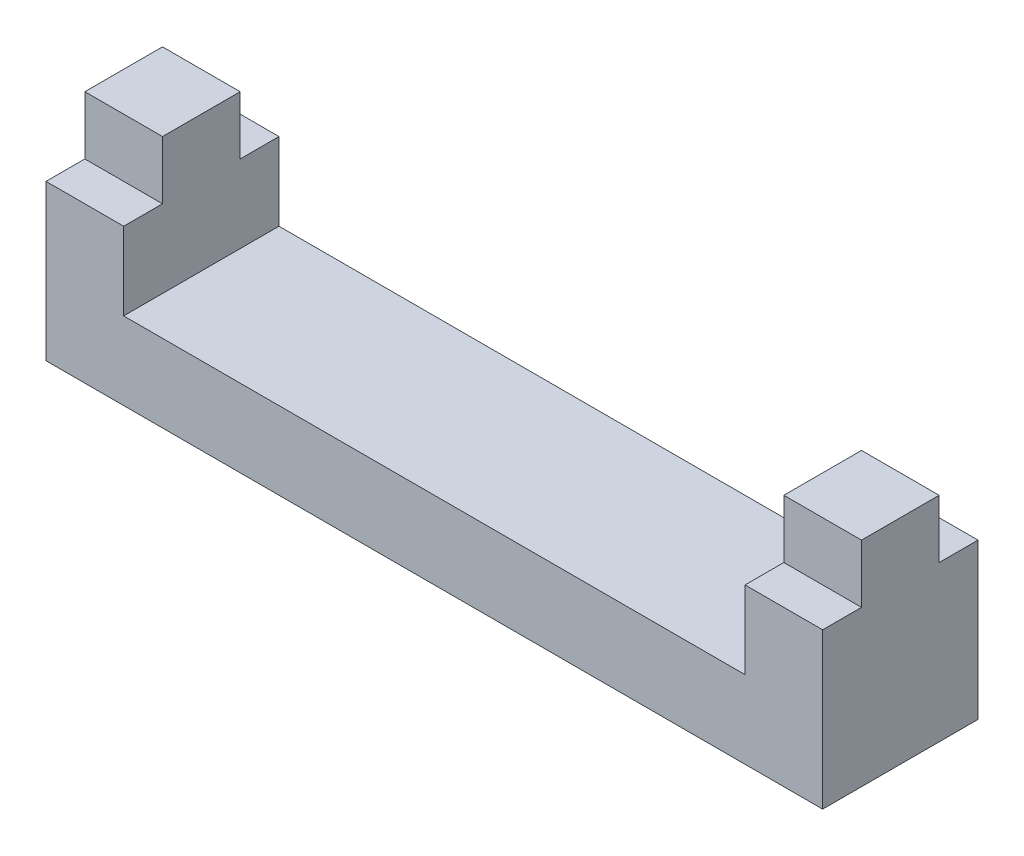
SolidWorks part; units mm, degrees
ref_plane "Front Plane" through (0, 0, 0) normal (0, 0, 1) x (1, 0, 0)
ref_plane "Top Plane" through (0, 0, 0) normal (0, 1, 0) x (1, 0, 0)
ref_plane "Right Plane" through (0, 0, 0) normal (1, 0, 0) x (0, 0, -1)
sketch "Sketch1" plane through (0, 0, 0) normal (0, 0, 1) x (1, 0, 0)
  line L0 (2, 2) -> (18, 2)
  line L1 (0, 0) -> (20, 0)
  line L7 (20, 5.5) -> (18, 5.5)
  line L8 (18, 2) -> (18, 5.5)
  line L11 (0, 5.5) -> (2, 5.5)
  line L12 (2, 2) -> (2, 5.5)
  line L13 (0, 5.5) -> (0, 0)
  line L14 (20, 0) -> (20, 5.5)
  dimension "D1" = 16
  dimension "D2" = 20
  dimension "D3" = 2
  dimension "D4" = 5.5
extrude "Boss-Extrude1" add sketch "Sketch1" along normal blind 2 and the other way blind 2
sketch "Sketch2" plane through (0, 0, 0) normal (-1, 0, 0) x (0, 0, 1)
  line L0 (0, 0) -> (0, 5.5) construction
  line L1 (-2, 5.5) -> (-1, 5.5)
  line L2 (-2, 5.5) -> (-2, 4)
  line L3 (-2, 4) -> (-1, 4)
  line L4 (-1, 5.5) -> (-1, 4)
  line L5 (-2, 5.5) -> (2, 5.5) construction
  dimension "D1" = 1.5
  dimension "D2" = 1
extrude "Cut-Extrude1" cut sketch "Sketch2" against normal through all both and the other way through all
mirror "Mirror1" about plane through (0, 0, 0) normal (0, 0, 1) of "Cut-Extrude1"
